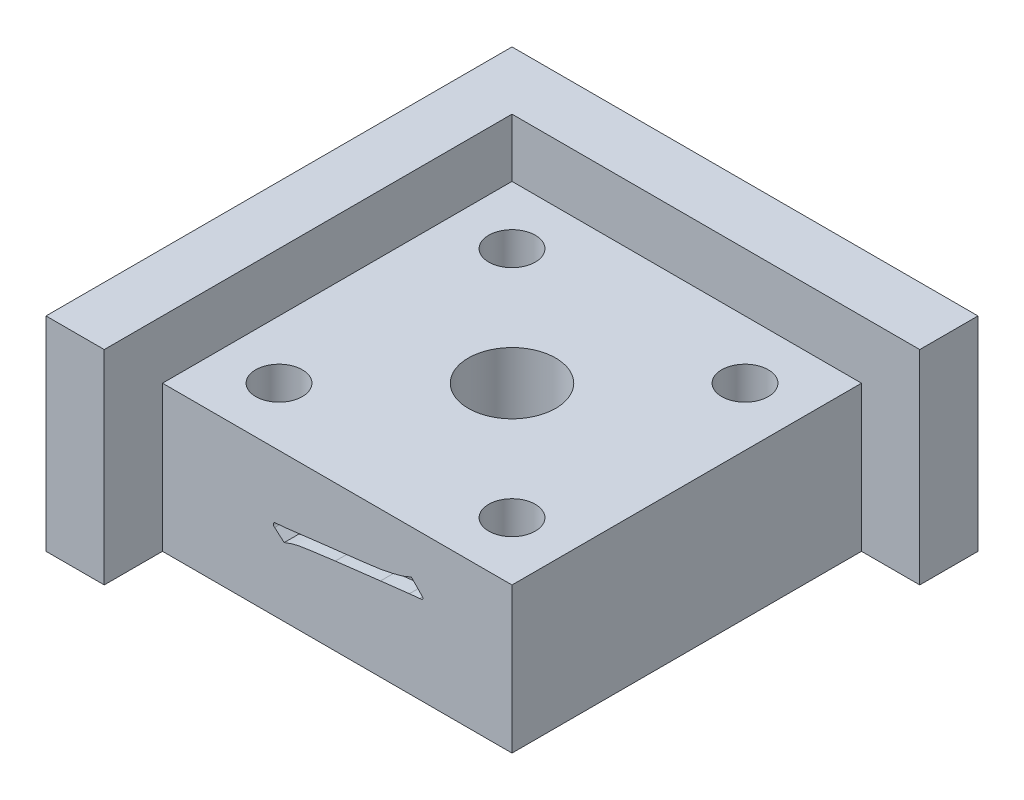
SolidWorks part; units mm, degrees
ref_plane "前视基准面" through (0, 0, 0) normal (0, 0, 1) x (1, 0, 0)
ref_plane "上视基准面" through (0, 0, 0) normal (0, 1, 0) x (1, 0, 0)
ref_plane "右视基准面" through (0, 0, 0) normal (1, 0, 0) x (0, 0, -1)
sketch "Sketch1" plane through (0, 0, 0) normal (0, 1, 0) x (1, 0, 0)
  line L0 (6, 0) -> (6, -6) construction
  line L1 (0, 0) -> (12, 0)
  line L2 (0, 0) -> (0, -12)
  line L3 (0, -12) -> (12, -12)
  line L4 (12, 0) -> (12, -12)
extrude "Boss-Extrude1" add sketch "Sketch1" against normal blind 3
shell "Shell2" thickness 1.8 removed face at (6, -3, 6)
sketch "Sketch3" plane through (0, 0, 0) normal (0, 1, 0) x (1, 0, 0)
  line L0 (0, 0) -> (0, 2) construction
  line L1 (0, 2) -> (-2, 2) construction
  line L2 (6, 2) -> (6, -6) construction
  line L3 (-2, 2) -> (14, 2)
  line L4 (-2, 2) -> (-2, -14)
  line L5 (-2, -14) -> (14, -14)
  line L6 (14, 2) -> (14, -14)
  circle A0 centre (6, -6) radius 1.5
  line M6 (0, 0) -> (0, -12)
  line M7 (0, -12) -> (12, -12)
  line M8 (12, -12) -> (12, 0)
  line M9 (12, 0) -> (0, 0)
extrude "Cut-Extrude3" cut sketch "Sketch3" against normal up to surface (1.8 mm away) contours A0 region at (6, 0, 6) up to face at (6, -1.8, 6)
extrude "Boss-Extrude2" add sketch "Sketch3<3>" along normal blind 2 contours A0 M9 M6 M7 M8 | L6 L3 L4 L5 M6 M9 M8 M7 region at (6, 0, -1.7737) region at (6, 0, 0.1697)
sketch "Sketch3<3>" plane through (0, 0, 0) normal (0, 1, 0) x (1, 0, 0) same geometry as "Sketch3"
sketch "Sketch4" plane through (0, 2, 0) normal (0, 1, 0) x (1, 0, 0)
  line L0 (-2, -14) -> (14, -14) construction
  line L1 (-2, 2) -> (0, 2)
  line L2 (-2, 2) -> (-2, -14)
  line L3 (-2, -14) -> (0, -14)
  line L4 (0, 2) -> (0, -14)
  line L5 (14, 2) -> (14, -14) construction
  line L6 (0, 2) -> (14, 2)
  line L7 (0, 2) -> (0, 0)
  line L8 (0, 0) -> (14, 0)
  line L9 (14, 2) -> (14, 0)
  line M10 (14, -14) -> (14, 2)
  line M11 (14, 2) -> (-2, 2)
  line M12 (-2, 2) -> (-2, -14)
  line M13 (-2, -14) -> (14, -14)
extrude "Boss-Extrude3" add sketch "Sketch4" along normal blind 2 contours L4 M11 M12 M13 | L4 L8 M10 M11 region at (-1, 2, 6) region at (7, 2, -1)
sketch "Sketch5" plane through (0, 0, 0) normal (0, -1, 0) x (1, 0, 0)
  line L1 (14, 14) -> (-2, 14)
  line L2 (14, 14) -> (14, -2)
  line L3 (14, -2) -> (-2, -2)
  line L4 (-2, 14) -> (-2, -2)
  line L5 (12, 12) -> (0, 12)
  line L6 (12, 12) -> (12, 0)
  line L7 (12, 0) -> (0, 0)
  line L8 (0, 12) -> (0, 0)
extrude "Boss-Extrude4" add sketch "Sketch5" along normal up to surface (3 mm away) up to face at (6, -3, 6)
sketch "Sketch6" plane through (0, 0, 14) normal (0, 0, 1) x (1, 0, 0)
  line L0 (-2, -3) -> (14, -3) construction
  line L1 (14, 2) -> (0, 2)
  line L2 (14, 2) -> (14, -3)
  line L3 (14, -3) -> (0, -3)
  line L4 (0, 2) -> (0, -3)
extrude "Cut-Extrude4" cut sketch "Sketch6" against normal blind 2
sketch "Sketch7" plane through (14, 0, 0) normal (1, 0, 0) x (0, 0, -1)
  line L1 (0, 2) -> (-12, 2)
  line L2 (0, 2) -> (0, -3)
  line L3 (0, -3) -> (-12, -3)
  line L4 (-12, 2) -> (-12, -3)
extrude "Cut-Extrude5" cut sketch "Sketch7" against normal blind 2
sketch "Sketch8" plane through (0, 0, 12) normal (0, 0, 1) x (1, 0, 0)
  text T0 " 一"
extrude "Cut-Extrude6" cut sketch "Sketch8" against normal blind 0.5
sketch "Sketch9" plane through (0, 2, 0) normal (0, 1, 0) x (1, 0, 0)
  line L0 (0, -12) -> (2, -12) construction
  line L1 (12, -12) -> (0, -12) construction
  line L2 (2, -12) -> (2, -10) construction
  line L3 (12, -12) -> (10, -12) construction
  line L4 (10, -12) -> (10, -10) construction
  line L5 (0, 0) -> (2, 0) construction
  line L6 (0, 0) -> (14, 0) construction
  line L7 (2, 0) -> (2, -2) construction
  line L8 (12, 0) -> (10, 0) construction
  line L9 (10, 0) -> (10, -2) construction
  circle A1 centre (2, -10) radius 0.8
  circle A2 centre (10, -10) radius 0.8
  circle A3 centre (2, -2) radius 0.8
  circle A4 centre (10, -2) radius 0.8
  point P1 (0, 0)
extrude "Cut-Extrude7" cut sketch "Sketch9" against normal through all contours A2 | A3 | A4 | A1
